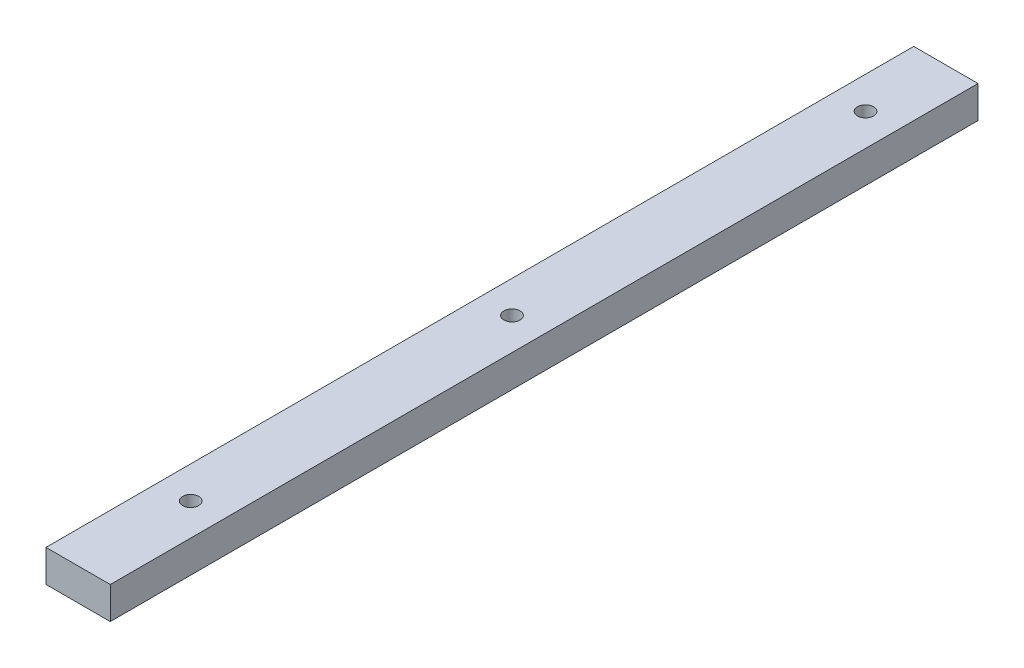
SolidWorks part; units mm, degrees
ref_plane "Front Plane" through (0, 0, 0) normal (0, 0, 1) x (1, 0, 0)
ref_plane "Top Plane" through (0, 0, 0) normal (0, 1, 0) x (1, 0, 0)
ref_plane "Right Plane" through (0, 0, 0) normal (1, 0, 0) x (0, 0, -1)
sketch "Sketch1" plane through (0, 0, 0) normal (0, 0, 1) x (1, 0, 0)
  line L1 (0, 0) -> (50.8, 0)
  line L2 (0, 0) -> (0, 25.4)
  line L3 (0, 25.4) -> (50.8, 25.4)
  line L4 (50.8, 0) -> (50.8, 25.4)
  dimension "D1" = 25.4
  dimension "D2" = 50.8
extrude "Boss-Extrude1" add sketch "Sketch1" along normal blind 685.8
sketch "Sketch2" plane through (0, 25.4, 0) normal (0, 1, 0) x (1, 0, 0)
  line L0 (50.8, 0) -> (0, 0) construction
  line L1 (50.8, -685.8) -> (50.8, 0) construction
  line L2 (50.8, -685.8) -> (0, -685.8) construction
  circle A0 centre (25.4, -63.5) radius 6.35
  circle A1 centre (25.4, -596.9) radius 6.35
  circle A2 centre (25.4, -342.9) radius 6.35
  point P10 (21.0221, -152.2523)
  point P13 (0, 0)
  point P14 (0, 0)
  point P15 (50.8, -342.9)
  dimension "D1" = 12.7
  dimension "D4" = 12.7
  dimension "D7" = 12.7
  dimension "D2" = 63.5
  dimension "D3" = 25.4
  dimension "D5" = 0
  dimension "D6" = 88.9
extrude "Cut-Extrude1" cut sketch "Sketch2" against normal blind 254
